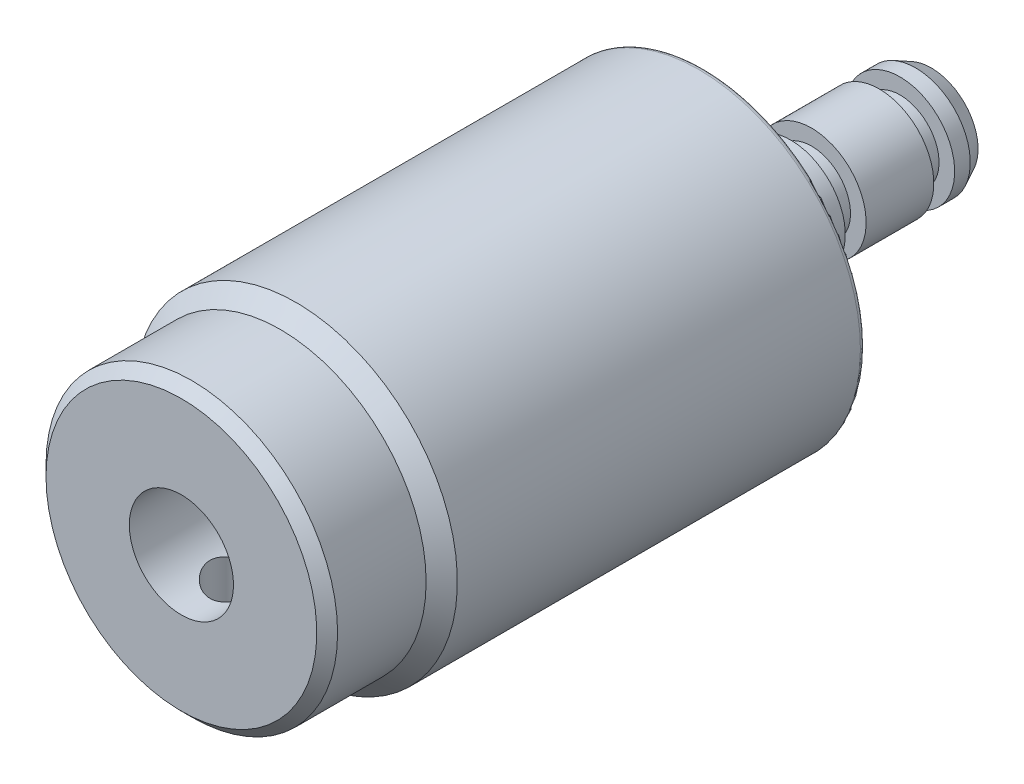
SolidWorks part; units mm, degrees
ref_plane "Top" through (0, 0, 0) normal (0, 0, 1) x (1, 0, 0)
ref_plane "Front" through (0, 0, 0) normal (0, 1, 0) x (1, 0, 0)
ref_plane "Right" through (0, 0, 0) normal (1, 0, 0) x (0, 0, -1)
sketch "Body Sketch" plane through (0, 0, 0) normal (0, 1, 0) x (1, 0, 0)
  line L0 (0, 0) -> (0, -36) construction
  line L1 (2.5, -36) -> (7, -36)
  line L2 (7, -36) -> (7, -31.25)
  line L3 (7, -31.25) -> (7.75, -30.5)
  line L4 (7.75, -30.5) -> (7.75, -10.9)
  line L5 (7.75, -10.9) -> (6, -10.9)
  line L6 (6, -10.9) -> (2.625, -7.75)
  line L7 (2.625, -7.75) -> (2.625, -6.75)
  line L8 (2.625, -6.75) -> (1.875, -6.75)
  line L9 (1.875, -6.75) -> (1.875, -5.75)
  line L10 (1.875, -5.75) -> (2.625, -5.75)
  line L11 (2.625, -5.75) -> (2.625, -2.5)
  line L12 (2.625, -2.5) -> (1.875, -2.5)
  line L13 (1.875, -2.5) -> (1.875, -1.5)
  line L14 (1.875, -1.5) -> (2.625, -1.5)
  line L15 (2.625, -1.5) -> (2.625, -0.75)
  line L16 (2.625, -0.75) -> (2.25, 0)
  line L17 (2.25, 0) -> (1.5, 0)
  line L18 (1.5, 0) -> (1.5, -30.4226)
  line L19 (2.5, -36) -> (2.5, -31)
  line L20 (2.5, -31) -> (1.5, -30.4226)
  dimension "D1" = 7
  dimension "D2" = 4.75
  dimension "D3" = 0.75
  dimension "D4" = 19.6
  dimension "D5" = 0.75
  dimension "D6" = 0.75
  dimension "D7" = 0.75
  dimension "D8" = 1
  dimension "D9" = 2.625
  dimension "D10" = 1.5
  dimension "D11" = 7.75
  dimension "D12" = 36
  dimension "D13" = 1
  dimension "D14" = 3.25
  dimension "D15" = 1
  dimension "D16" = 6
  dimension "D17" = 0.75
  dimension "D18" = 2.5
  dimension "D19" = 5
  dimension "D20" = 120
revolve "Body Revolve" add sketch "Body Sketch" angle 360 about L0
fillet "Outside Bottom Fillet" radius 0.25 1 edges at (-7.75, 0, 10.9)
chamfer "Top Chamfer" distance 0.5 angle 45 1 edges at (-7, 0, 36)
hole_wizard "M3x0.5 Tapped Hole" positions "M3 Position Sketch" profile "M3 Profile Sketch" tap size "M3x0.5" standard "ANSI Metric" end condition up to next
sketch3d "M3 Position Sketch"
  line L2 (0, 0, 0) -> (0, 0, 35.5) construction
  line L3 (0, 0, 30.4226) -> (0, 0, 0) construction
  line L4 (0, 0, 35.5) -> (0, 0, 36) construction
  line L5 (0, 0, 35.5) -> (0, -7, 35.5) construction
  line L7 (0, -7, 35.5) -> (0, -7, 33.375) construction
  circle A0 centre (0, 0, 35.5) radius 7 construction
  point P0 (0, -7, 33.375)
  point P7 (0, 0, 28.5)
  dimension "D1" = 2.125
  dimension "D2" = 7
sketch "M3 Profile Sketch" plane through (0, -7, 33.375) normal (1, 0, 0) x (0, 0, -1)
  line L0 (0, 0) -> (0, 4.5)
  line L1 (0, 4.5) -> (1.25, 4.5)
  line L2 (1.25, 4.5) -> (1.25, 0)
  line L5 (1.25, 0) -> (0, 0)
  line L11 (0, -6.35) -> (0, 107.95) construction
  dimension "Thru Tap Drill Dia." = 2.5
  dimension "Thru Tap Drill Depth" = 4.5
cosmetic thread "M3 Hole Thread" parameters "D2"=3
equation "\"D1@M3 Position Sketch\"=2.375mm-0.25"
